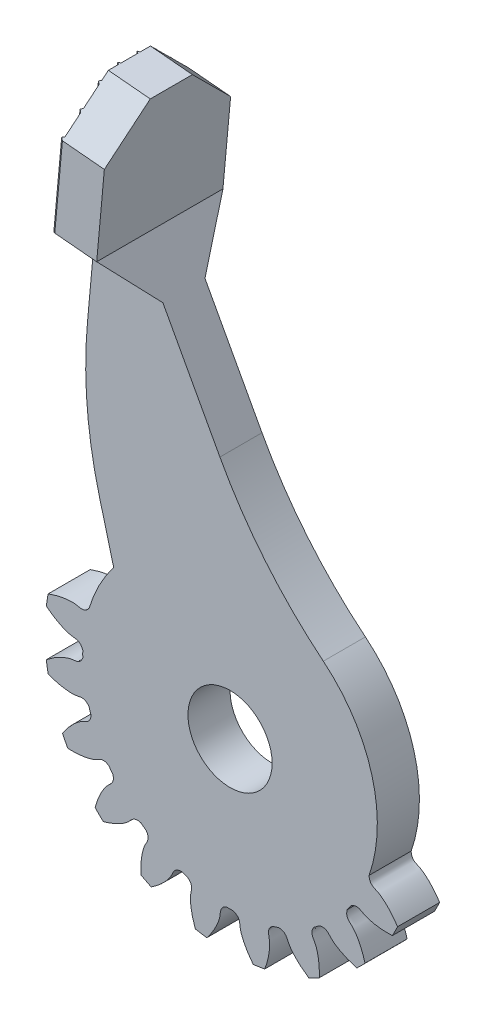
SolidWorks part; units mm, degrees
ref_plane "前视基准面" through (0, 0, 0) normal (0, 0, 1) x (1, 0, 0)
ref_plane "上视基准面" through (0, 0, 0) normal (0, 1, 0) x (1, 0, 0)
ref_plane "右视基准面" through (0, 0, 0) normal (1, 0, 0) x (0, 0, -1)
other "Configuration Table"
sketch "草图1" plane through (0, 0, 0) normal (0, 0, 1) x (1, 0, 0)
  circle A0 centre (0, 0) radius 22
extrude "凸台-拉伸1" add sketch "草图1" along normal blind 30
ref_axis "基准轴1" through (0, 0, 30) along (0, 0, -1)
sketch "草图2" plane through (0, 0, 0) normal (0, 0, 1) x (1, 0, 0)
  line L0 (0, 0) -> (0, 22) construction
  circle A0 centre (0, 0) radius 22 construction
  arc A1 (0.3866, 17.4957) -> (-0.3866, 17.4957) centre (0, 0) ccw
  arc A2 (6.3623, 24.9965) -> (-6.3623, 24.9965) centre (0, 0) ccw
  spline S0 degree 3 poles (0.3866, 17.4957) (1.2224, 17.787) (1.1142, 18.3742) (1.2258, 18.94) (1.2378, 18.9951) (1.2526, 19.0573) (1.2706, 19.1264) (1.292, 19.2024) (1.317, 19.2851) (1.3461, 19.3745) (1.3793, 19.4704) (1.4171, 19.5726) (1.4597, 19.6811) (1.5073, 19.7956) (1.5603, 19.9161) (1.6187, 20.0423) (1.683, 20.174) (1.7534, 20.3112) (1.83, 20.4535) (1.9132, 20.6008) (2.0031, 20.7529) (2.1, 20.9095) (2.204, 21.0705) (2.3155, 21.2356) (2.4346, 21.4046) (2.5615, 21.5772) (2.6964, 21.7533) (2.8395, 21.9324) (2.991, 22.1145) (3.1509, 22.2992) (3.3196, 22.4862) (3.4971, 22.6753) (3.6837, 22.8662) (3.8793, 23.0586) (4.0843, 23.2521) (4.2986, 23.4467) (4.5225, 23.6418) (4.7559, 23.8372) (4.9991, 24.0327) (5.2521, 24.2278) (5.515, 24.4223) (5.8829, 24.6833) (6.1679, 24.8727) (6.3623, 24.9965) knots 0 0 0 0 0.165916 0.170906 0.176664 0.183189 0.190482 0.198542 0.207371 0.216967 0.22733 0.238462 0.250361 0.263027 0.276462 0.290664 0.305634 0.321371 0.337876 0.355149 0.37319 0.391998 0.411574 0.431917 0.453028 0.474907 0.497554 0.520968 0.54515 0.570099 0.595817 0.622302 0.649554 0.677575 0.706363 0.735918 0.766242 0.797333 0.829191 0.861818 0.895212 0.929373 1 1 1 1
  spline S1 degree 3 poles (-0.3866, 17.4957) (-1.2224, 17.787) (-1.1142, 18.3742) (-1.2258, 18.94) (-1.2378, 18.9951) (-1.2526, 19.0573) (-1.2706, 19.1264) (-1.292, 19.2024) (-1.317, 19.2851) (-1.3461, 19.3745) (-1.3793, 19.4704) (-1.4171, 19.5726) (-1.4597, 19.6811) (-1.5073, 19.7956) (-1.5603, 19.9161) (-1.6187, 20.0423) (-1.683, 20.174) (-1.7534, 20.3112) (-1.83, 20.4535) (-1.9132, 20.6008) (-2.0031, 20.7529) (-2.1, 20.9095) (-2.204, 21.0705) (-2.3155, 21.2356) (-2.4346, 21.4046) (-2.5615, 21.5772) (-2.6964, 21.7533) (-2.8395, 21.9324) (-2.991, 22.1145) (-3.1509, 22.2992) (-3.3196, 22.4862) (-3.4971, 22.6753) (-3.6837, 22.8662) (-3.8793, 23.0586) (-4.0843, 23.2521) (-4.2986, 23.4467) (-4.5225, 23.6418) (-4.7559, 23.8372) (-4.9991, 24.0327) (-5.2521, 24.2278) (-5.515, 24.4223) (-5.8829, 24.6833) (-6.1679, 24.8727) (-6.3623, 24.9965) knots 0 0 0 0 0.165916 0.170906 0.176664 0.183189 0.190482 0.198542 0.207371 0.216967 0.22733 0.238462 0.250361 0.263027 0.276462 0.290664 0.305634 0.321371 0.337876 0.355149 0.37319 0.391998 0.411574 0.431917 0.453028 0.474907 0.497554 0.520968 0.54515 0.570099 0.595817 0.622302 0.649554 0.677575 0.706363 0.735918 0.766242 0.797333 0.829191 0.861818 0.895212 0.929373 1 1 1 1
extrude "切除-拉伸1" cut sketch "草图2" along normal through all
pattern_circular "阵列(圆周)1" count 20 every 18 about axis through (0, 0, 30) along (0, 0, -1) of "切除-拉伸1"
sketch "草图3" plane through (0, 0, 0) normal (0, 0, 1) x (1, 0, 0)
  circle A0 centre (0, 0) radius 20 construction
  dimension "Dn" = 40
sketch "草图4" plane through (0, 0, 30) normal (0, 0, 1) x (1, 0, 0)
  circle A0 centre (0, 0) radius 42.426
extrude "切除-拉伸2" cut sketch "草图4" against normal blind 25
sketch "草图5" plane through (0, 0, 5) normal (0, 0, 1) x (1, 0, 0)
  circle A0 centre (0, 0) radius 5
  dimension "D1" = 10
extrude "切除-拉伸3" cut sketch "草图5" against normal blind 30
sketch "草图6" plane through (0, 0, 5) normal (0, 0, 1) x (1, 0, 0)
  line L1 (-20.7585, 6.7448) -> (-16.6435, 5.4078)
  line L2 (-20.7585, 6.7448) -> (-21.7192, 7.057)
  line L3 (16.6435, -5.4078) -> (21.7192, -7.057)
  arc A0 (16.6435, -5.4078) -> (-16.6435, 5.4078) centre (0, 0) ccw
  arc A1 (21.7192, -7.057) -> (-21.7192, 7.057) centre (0, 0) ccw
  point P4 (-20.3328, 8.0551)
  dimension "D1" = 35
extrude "切除-拉伸4" cut sketch "草图6" against normal through all both and the other way through all
sketch "草图8" plane through (0, 0, 5) normal (0, 0, 1) x (1, 0, 0)
  line L4 (-33.0933, 6.7448) -> (-29.2504, 6.7448)
  line L7 (-17.7439, 25.5998) -> (-16.8339, 35.5583)
  line L8 (-13.3617, 11.661) -> (-17.7439, 25.5998)
  line L9 (-9.8456, 4.9715) -> (-13.3617, 11.661)
  line L10 (-6.0663, 4.2749) -> (-9.8456, 4.9715)
  line L11 (-7.1169, 16.1507) -> (-6.0663, 4.2749)
  line L12 (-14.7564, 25.3268) -> (-7.1169, 16.1507)
  line L13 (-13.8463, 35.2853) -> (-14.7564, 25.3268)
  line L14 (-16.8339, 35.5583) -> (-13.8463, 35.2853)
  arc M2 (16.52, -5.7742) -> (-16.7589, 5.0388) centre (0, 0) ccw
extrude "凸台-拉伸2" add sketch "草图8" against normal up to surface (5 mm away) contours L14 L7 L8 L9 L11 L12 L13 M2 | L11 L9 L10 M2 region at (-13.7852, 22.4105, 5) region at (-9.062, 9.9199, 5) up to face at (5, 0, 0)
sketch "草图9" plane through (0, 0, 5) normal (0, 0, 1) x (1, 0, 0)
  line L5 (-17.7439, 25.5998) -> (-14.4567, 61.5711)
  line L7 (-14.4567, 61.5711) -> (-9.4775, 61.1161)
  line L8 (-9.4775, 61.1161) -> (-10.8425, 46.1783)
  line L9 (-10.8425, 46.1783) -> (14.9378, -1.3651)
  line L10 (-9.0701, 10.3552) -> (5.6967, 9.2423)
  line L11 (5.6967, 9.2423) -> (8.5892, -3.0315)
  line L12 (-17.7439, 25.5998) -> (-11.2619, 1.0292)
  line L13 (-11.2619, 1.0292) -> (-9.0701, 10.3552)
  line L25 (8.5892, -3.0315) -> (14.9378, -1.3651)
  dimension "D2" = 15
  dimension "D5" = 5
extrude "凸台-拉伸3" add sketch "草图9" against normal up to surface (5 mm away) contours L12 L13 L10 L11 L25 L9 L8 L7 L5 up to face at (-5.0713, -5.5228, 0)
ref_plane "基准面1" through (0, 0, 2.5) normal (0, 0, -1) x (-1, 0, 0)
sketch "草图10" plane through (0, 0, 2.5) normal (0, 0, -1) x (-1, 0, 0)
  line L0 (14.4567, 61.5711) -> (9.4775, 61.1161)
  line L1 (9.4775, 61.1161) -> (10.8425, 46.1783)
  line L2 (10.8425, 46.1783) -> (15.8218, 46.6334)
  line L3 (17.7439, 25.5998) -> (14.4567, 61.5711) construction
  line L4 (15.8218, 46.6334) -> (14.4567, 61.5711)
extrude "凸台-拉伸4" add sketch "草图10" along normal mid plane 15
chamfer "倒角1" distance 5 angle 45 2 edges at (-13.3322, 46.4059, 0) (-13.3322, 46.4059, 5)
fillet "圆角1" radius 50 1 edges at (5.1241, 16.733, 2.5)
fillet "圆角2" radius 50 1 edges at (-17.7439, 25.5998, 2.5)
chamfer "倒角2" distance 5 angle 45 2 edges at (-11.9671, 61.3436, -5) (-11.9671, 61.3436, 10)
sketch "草图11" plane through (5.4603, 59.751, 0) normal (0.091, 0.9959, 0) x (0.9959, -0.091, 0)
  line L0 (-20, 5) -> (-20, 4.7113)
  line L1 (-20, 5) -> (-20.25, 4.8557)
  line L2 (-20.25, 4.8557) -> (-20, 4.7113)
  line L3 (-20, 3) -> (-20, 2.7113)
  line L4 (-20, 3) -> (-20.25, 2.8557)
  line L5 (-20.25, 2.8557) -> (-20, 2.7113)
  line L6 (-20, 0) -> (-20, 5) construction
  line L7 (-20, 1) -> (-20, 0.7113)
  line L8 (-20, 1) -> (-20.25, 0.8557)
  line L9 (-20.25, 0.8557) -> (-20, 0.7113)
  line L10 (-20, -1.2113) -> (-20, -1.5)
  line L11 (-20, -1.2113) -> (-20.25, -1.3557)
  line L12 (-20.25, -1.3557) -> (-20, -1.5)
  line L13 (-20, 0) -> (-20, -5) construction
  line L14 (-20, -3.5) -> (-20, -3.7887)
  line L15 (-20, -3.5) -> (-20.25, -3.6443)
  line L16 (-20.25, -3.6443) -> (-20, -3.7887)
  line L17 (-15, 0) -> (-20, 0) construction
  line L18 (-20, -5) -> (-15, -5) construction
  line L19 (-20, -7.7113) -> (-20, -8)
  line L20 (-20, -7.7113) -> (-20.25, -7.8557)
  line L21 (-20.25, -7.8557) -> (-20, -8)
  line L22 (-20, -9.7113) -> (-20, -10)
  line L23 (-20, -9.7113) -> (-20.25, -9.8557)
  line L24 (-20.25, -9.8557) -> (-20, -10)
  line L25 (-20, -5.7113) -> (-20, -6)
  line L26 (-20, -5.7113) -> (-20.25, -5.8557)
  line L27 (-20.25, -5.8557) -> (-20, -6)
  line L31 (-20, -10) -> (-20, -5) construction
  point P30 (0, 0)
  dimension "D1" = 0.25
  dimension "D2" = 60
  dimension "D3" = 60
  dimension "D4" = 0.25
  dimension "D5" = 60
  dimension "D6" = 60
  dimension "D7" = 2
  dimension "D8" = 0.25
  dimension "D9" = 120
  dimension "D10" = 2
  dimension "D11" = 120
  dimension "D12" = 0.25
  dimension "D13" = 60
  dimension "D14" = 60
  dimension "D15" = 0.25
  dimension "D16" = 60
  dimension "D17" = 60
  dimension "D18" = 1.5
  dimension "D19" = 1.5
  dimension "D20" = 0.25
  dimension "D21" = 60
  dimension "D22" = 60
  dimension "D23" = 0.25
  dimension "D24" = 60
  dimension "D25" = 60
  dimension "D26" = 2
  dimension "D27" = 2
  dimension "D28" = 0.25
  dimension "D29" = 60
  dimension "D30" = 60
  dimension "D31" = 2
extrude "凸台-拉伸5" add sketch "草图11" against normal blind 30
sketch "草图12" plane through (-19.917, 1.8201, 0) normal (-0.9959, 0.091, 0) x (0, 0, 1)
  line L0 (0, 60) -> (-5, 55)
  line L1 (-5, 55) -> (-5, 45)
  line L4 (0, 40) -> (-5, 45)
  line L5 (0, 40) -> (5, 40)
  line L6 (5, 40) -> (10, 45)
  line L7 (0, 60) -> (5, 60)
  line L8 (5, 60) -> (10, 55)
  line L9 (10, 55) -> (10, 45)
  line L13 (-15.8927, 16.4052) -> (16.9674, 16.4052)
  line L14 (-15.8927, 16.4052) -> (-15.8927, -20.9409)
  line L15 (-15.8927, -20.9409) -> (16.9674, -20.9409)
  line L16 (16.9674, 16.4052) -> (16.9674, -20.9409)
extrude "切除-拉伸6" cut sketch "草图12" along normal blind 13 flip side to cut
